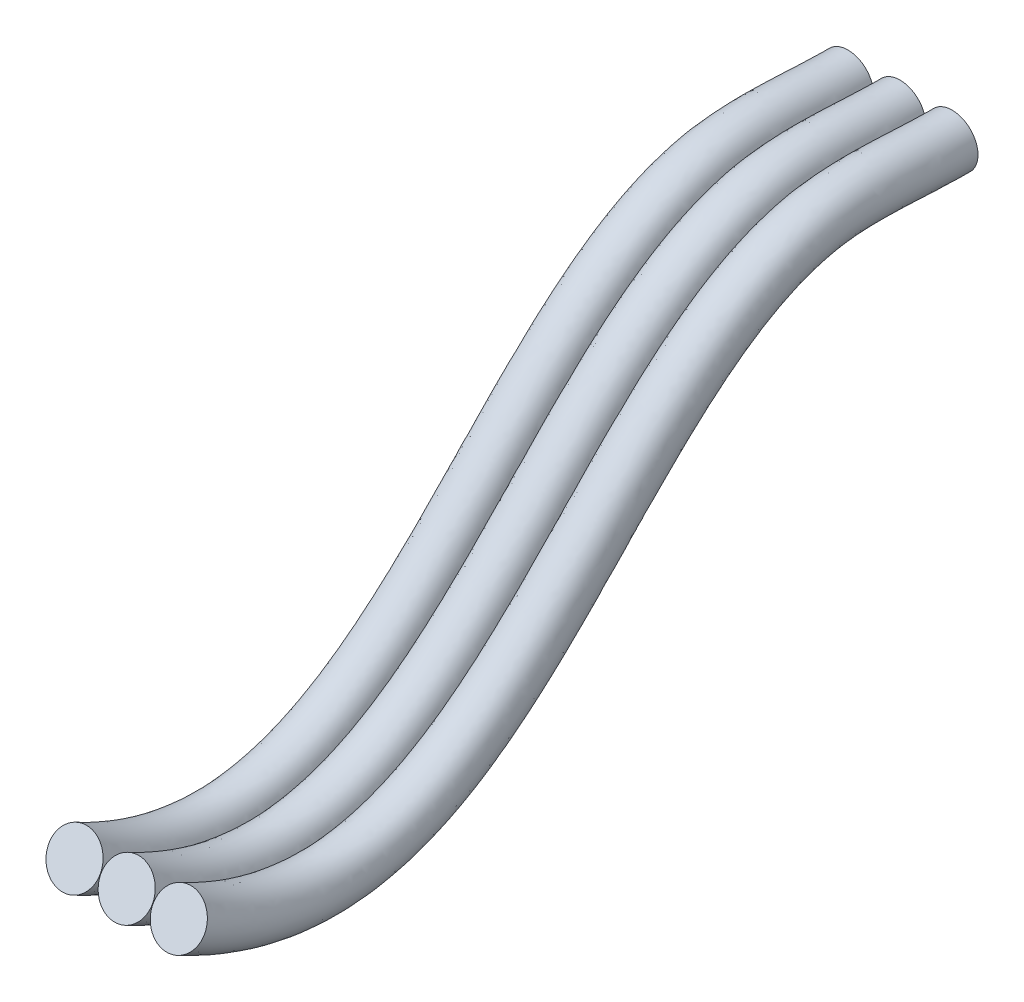
SolidWorks part; units mm, degrees
ref_plane "Front Plane" through (0, 0, 0) normal (0, 0, 1) x (1, 0, 0)
ref_plane "Top Plane" through (0, 0, 0) normal (0, 1, 0) x (1, 0, 0)
ref_plane "Right Plane" through (0, 0, 0) normal (1, 0, 0) x (0, 0, -1)
sketch "Sketch2" plane through (0, 0, 0) normal (1, 0, 0) x (0, 0, -1)
  line L1 (0, 3.8) -> (0, 7) construction
  spline S0 degree 3 poles (0, 5.4) (-1.3743, 5.4014) (-10.4185, 6.6895) (-14.2154, -8.6498) (-23.9233, -3.5067) knots 0 0 0 0 0.155478 1 1 1 1
  point P4 (0, 0)
sketch "Sketch3" plane through (0, 0, 0) normal (0, 0, 1) x (1, 0, 0)
  line L0 (0, 3.8) -> (0, 7) construction
  line L2 (-2.45, 6.4974) -> (-2.45, 4.303) construction
  line L3 (-2.45, 6.5) -> (-2.45, 4.3) construction
  line L6 (1.6127, 5.4) -> (-1.6127, 5.4) construction
  circle A0 centre (0, 5.4) radius 0.8
  circle A1 centre (-1.6127, 5.4) radius 0.8
  circle A2 centre (1.6127, 5.4) radius 0.8
  dimension "D1" = 0.0127
  dimension "D2" = 0.0127
  dimension "D3" = 1.6
sweep "Sweep2" add profiles "Sketch3" path "Sketch2"
